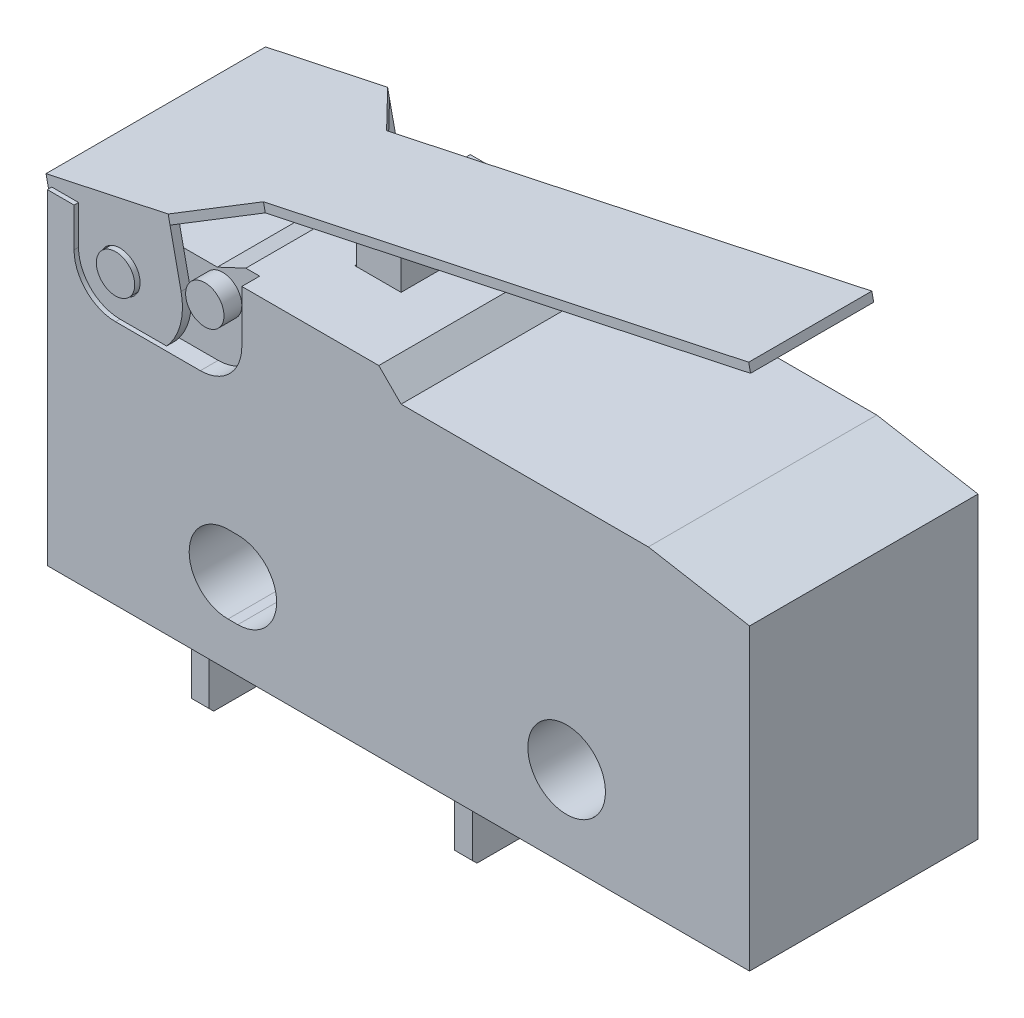
SolidWorks part; units mm, degrees
ref_plane "Front" through (0, 0, 0) normal (0, 0, 1) x (1, 0, 0)
ref_plane "Top" through (0, 0, 0) normal (0, 1, 0) x (1, 0, 0)
ref_plane "Right" through (0, 0, 0) normal (1, 0, 0) x (0, 0, -1)
sketch "Sketch2" plane through (0, 0, 0) normal (0, 0, 1) x (1, 0, 0)
  line L0 (-4.8514, 3.4671) -> (-4.572, 3.4671)
  line L1 (9.9949, 8.509) -> (7.1139, 9.017)
  line L2 (-9.9949, 9.271) -> (-9.9949, 0)
  line L3 (-9.9949, 0) -> (9.9949, 0)
  line L4 (9.9949, 8.509) -> (9.9949, 0)
  line L5 (-4.8514, 1.2573) -> (-4.572, 1.2573)
  line L6 (-4.7117, 3.4671) -> (-4.7117, 1.2573) construction
  line L7 (4.7879, 2.3622) -> (-4.572, 2.3622) construction
  line L8 (7.1139, 9.017) -> (0.0762, 9.017)
  line L9 (0.0762, 9.017) -> (-0.5588, 9.652)
  line L10 (-0.5588, 9.652) -> (-4.8514, 9.652)
  line L11 (-4.8514, 9.652) -> (-5.6646, 9.271)
  line L12 (-5.6646, 9.271) -> (-9.9949, 9.271)
  line L13 (-2.7051, 9.652) -> (-2.7051, 2.3622) construction
  line L14 (-4.8514, 9.652) -> (-4.8514, 3.4671) construction
  circle A0 centre (4.7879, 2.3622) radius 1.1049
  arc A1 (-4.8514, 3.4671) -> (-4.8514, 1.2573) centre (-4.8514, 2.3622) ccw
  arc A2 (-4.572, 1.2573) -> (-4.572, 3.4671) centre (-4.572, 2.3622) ccw
  dimension "D4" = 5.207
  dimension "D5" = 2.2098
  dimension "D6" = 2.4892
  dimension "D7" = 6.6548
  dimension "D8" = 7.2898
  dimension "D9" = 7.493
  dimension "D13" = 6.9088
  dimension "D1" = 19.9898
  dimension "D2" = 2.3622
  dimension "D3" = 9.4996
  dimension "D10" = 0.508
  dimension "D11" = 10
  dimension "D12" = 135
extrude "Extrude1" add sketch "Sketch2" along normal mid plane 6.5024
sketch "Sketch3" plane through (0, 0, 0) normal (0, 0, 1) x (1, 0, 0)
  line L0 (-3.3401, 9.271) -> (-3.3401, 10.6393)
  line L1 (-2.7051, 9.271) -> (-2.7051, 9.8462) construction
  line L2 (-2.0701, 10.6393) -> (-2.0701, 9.271)
  line L3 (-2.0701, 9.271) -> (-3.3401, 9.271)
  line L4 (-3.3401, 10.6393) -> (-2.0701, 10.6393) construction
  line L5 (-2.7051, 9.652) -> (-2.7051, 2.3622) construction
  line L6 (-5.6646, 9.271) -> (-9.9949, 9.271) construction
  arc A0 (-3.3401, 10.6393) -> (-2.0701, 10.6393) centre (-2.7051, 9.8462) cw
  arc A1 (-4.8514, 3.4671) -> (-4.8514, 1.2573) centre (-4.8514, 2.3622) ccw construction
  dimension "D1" = 8.5
  dimension "D3" = 1.016
  dimension "D2" = 1.27
extrude "Extrude2" add sketch "Sketch3" along normal mid plane 2.2098 separate body
sketch "Sketch4" plane through (0, 9.652, 0) normal (0, 1, 0) x (-1, 0, 0)
  line L0 (2.0701, -1.1049) -> (3.3401, -1.1049) construction
  line L1 (3.3401, 1.1049) -> (3.3401, -1.1049) construction
  line L2 (2.0701, 1.1049) -> (2.0701, -1.1049) construction
  line L3 (3.3401, 1.1049) -> (2.0701, 1.1049) construction
  line L4 (2.0701, -1.1049) -> (3.3401, -1.1049) construction
  line L5 (3.3401, 1.1049) -> (3.3401, -1.1049) construction
  line L6 (2.0701, 1.1049) -> (2.0701, -1.1049) construction
  line L7 (3.3401, 1.1049) -> (2.0701, 1.1049) construction
  line L8 (3.3655, 1.1303) -> (3.3655, -1.1303)
  line L9 (2.0447, -1.1303) -> (3.3655, -1.1303)
  line L10 (2.0447, 1.1303) -> (2.0447, -1.1303)
  line L11 (3.3655, 1.1303) -> (2.0447, 1.1303)
  dimension "D1" = 0.0254
extrude "Cut-Extrude1" cut sketch "Sketch4" against normal blind 1.016
sketch "Sketch5" plane through (0, 0, 3.2512) normal (0, 0, 1) x (1, 0, 0)
  line L0 (-9.2329, 9.271) -> (-9.2329, 8.1661)
  line L1 (-8.0518, 6.985) -> (-5.6388, 6.985)
  line L2 (-4.4577, 8.1661) -> (-4.4577, 9.652)
  line L3 (-5.6646, 9.271) -> (-9.9949, 9.271) construction
  line L4 (-4.8514, 9.652) -> (-5.6646, 9.271) construction
  line L5 (-0.5588, 9.652) -> (-4.8514, 9.652) construction
  line L6 (-5.6646, 9.271) -> (-9.2329, 9.271)
  line L7 (-4.8514, 9.652) -> (-5.6646, 9.271)
  line L8 (-4.4577, 9.652) -> (-4.8514, 9.652)
  line L9 (-9.9949, 9.271) -> (-9.9949, 0) construction
  circle A0 centre (-5.5118, 8.6741) radius 0.5461
  circle A1 centre (-8.0518, 8.1661) radius 0.5461
  arc A2 (-9.2329, 8.1661) -> (-8.0518, 6.985) centre (-8.0518, 8.1661) ccw
  arc A3 (-5.6388, 6.985) -> (-4.4577, 8.1661) centre (-5.6388, 8.1661) ccw
  dimension "D4" = 0.0508
  dimension "D5" = 1.0922
  dimension "D6" = 2.54
  dimension "D7" = 0.508
  dimension "D1" = 0.762
  dimension "D2" = 0.508
  dimension "D3" = 0.635
extrude "Cut-Extrude2" cut sketch "Sketch5" against normal blind 0.508
mirror "Mirror1" about plane through (0, 0, 0) normal (0, 0, 1) of "Cut-Extrude2"
ref_plane "Plane1" through (-7.493, 0, 0) normal (1, 0, 0) x (0, 0, -1)
sketch "Sketch10" plane through (-7.493, 0, 0) normal (1, 0, 0) x (0, 0, -1)
  line L0 (-1.397, 0) -> (-1.397, -3.0734)
  line L1 (-1.27, -3.2004) -> (1.27, -3.2004)
  line L2 (1.397, -3.0734) -> (1.397, 0)
  line L3 (1.397, 0) -> (-1.397, 0)
  line L4 (0, -3.2004) -> (0, -1.7018) construction
  line L5 (0, 0) -> (0, -1.7018) construction
  line L6 (-1.397, -3.0734) -> (-1.27, -3.2004)
  line L7 (1.27, -3.2004) -> (1.397, -3.0734)
  circle A0 centre (0, -1.7018) radius 0.9017
  point P1 (-1.397, -3.2004)
  point P3 (1.397, -3.2004)
  dimension "D2" = 1.8034
  dimension "D1" = 3.2004
  dimension "D3" = 2.794
  dimension "D4" = 1.4986
  dimension "D5" = 0.127
  dimension "D6" = 45
  dimension "D7" = 0.127
  dimension "D8" = 45
extrude "Extrude6" add sketch "Sketch10" along normal mid plane 0.508
pattern_linear "LPattern1" count 2 spacing 7.493 along (1, 0, 0) of "Extrude6"
sketch "Sketch6" plane through (0, 0, 0) normal (0, 0, 1) x (1, 0, 0)
  line L0 (-10.1055, 9.271) -> (8.524, 13.2516)
  line L1 (8.524, 13.2516) -> (8.4709, 13.5)
  line L2 (8.4709, 13.5) -> (-10.1586, 9.5194)
  line L3 (-10.1586, 9.5194) -> (-10.1055, 9.271)
  line L4 (-5.6646, 9.271) -> (-9.2329, 9.271) construction
  line L10 (-10.1055, 9.271) -> (-9.7901, 7.7947) construction
  line L11 (-6.3135, 8.5375) -> (-6.629, 10.0138) construction
  circle A0 centre (4.7879, 2.3622) radius 1.1049 construction
  circle A2 centre (-8.0518, 8.1661) radius 0.5461 construction
  arc A6 (-9.7901, 7.7947) -> (-6.3135, 8.5375) centre (-8.0518, 8.1661) ccw construction
  dimension "D1" = 3.683
  dimension "D2" = 13.5
  dimension "D4" = 19.05
  dimension "D5" = 0.254
extrude "Extrude3" add sketch "Sketch6" along normal mid plane 3.5052 separate body
sketch "Sketch8" plane through (0, 0, 3.2512) normal (0, 0, 1) x (1, 0, 0)
  line L0 (-6.3135, 8.5375) -> (-6.629, 10.0138) construction
  line L1 (-10.1055, 9.271) -> (-9.7901, 7.7947) construction
  line L2 (-6.3135, 8.5375) -> (-6.6821, 10.2622)
  line L3 (-10.1586, 9.5194) -> (-9.7901, 7.7947)
  line L4 (8.4709, 13.5) -> (-10.1586, 9.5194) construction
  line L5 (-6.6821, 10.2622) -> (-10.1586, 9.5194)
  arc A1 (-9.7901, 7.7947) -> (-6.3135, 8.5375) centre (-8.0518, 8.1661) ccw construction
  arc A3 (-9.7901, 7.7947) -> (-6.3135, 8.5375) centre (-8.0518, 8.1661) ccw
  circle A5 centre (-8.0518, 8.1661) radius 0.5715
  circle A6 centre (-8.0518, 8.1661) radius 0.5715
  dimension "D1" = 0.0254
extrude "Extrude4" add sketch "Sketch8" against normal blind 0.254 from offset 0.127 separate body offset against normal yes
sketch "Sketch9" plane through (0, 0, 1.7526) normal (0, 0, 1) x (1, 0, 0)
  line L0 (-6.3135, 8.5375) -> (-6.629, 10.0138) construction
  line L1 (-10.1586, 9.5194) -> (-10.1055, 9.271) construction
  line L2 (-10.1055, 9.271) -> (8.524, 13.2516) construction
  line L3 (8.4709, 13.5) -> (-10.1586, 9.5194) construction
  line L4 (-6.629, 10.0138) -> (-6.6821, 10.2622)
  line L5 (-10.1586, 9.5194) -> (-10.1055, 9.271)
  line L6 (-10.1055, 9.271) -> (-6.629, 10.0138)
  line L7 (-6.6821, 10.2622) -> (-10.1586, 9.5194)
extrude "Extrude5" add sketch "Sketch9" along normal up to surface (1.1176 mm away) up to face at (-7.4803, 8.1661, 2.8702)
mirror "Mirror7" about plane through (0, 0, 0) normal (0, 0, 1) of bodies 116
combine bodies "Combine1" operation type add bodies to combine 118 114 116
chamfer "Chamfer1" distance 1.3716 angle 45 2 edges
